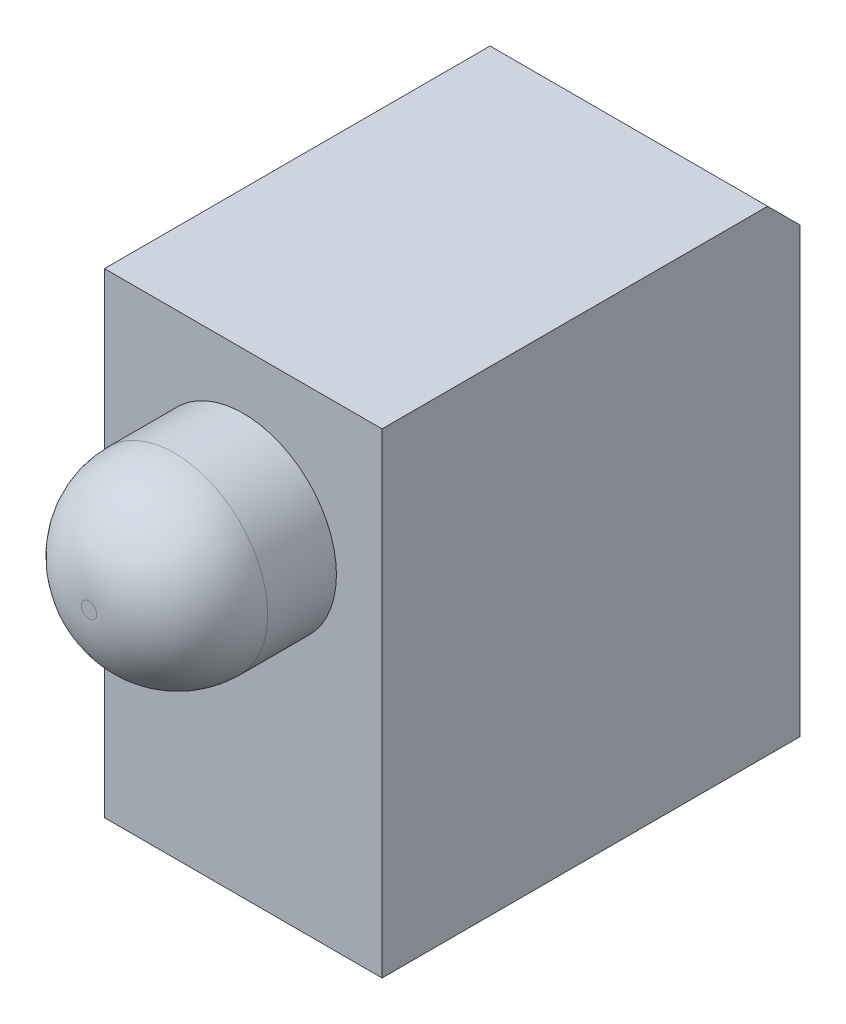
SolidWorks part; units mm, degrees
ref_plane "Front Plane" through (0, 0, 0) normal (0, 0, 1) x (1, 0, 0)
ref_plane "Top Plane" through (0, 0, 0) normal (0, 1, 0) x (1, 0, 0)
ref_plane "Right Plane" through (0, 0, 0) normal (1, 0, 0) x (0, 0, -1)
sketch "Sketch1" plane through (0, 0, 0) normal (1, 0, 0) x (0, 0, -1)
  line L1 (-3.25, -3.7) -> (3.25, -3.7)
  line L2 (-3.25, -3.7) -> (-3.25, 3.7)
  line L3 (-3.25, 3.7) -> (3.25, 3.7)
  line L4 (3.25, -3.7) -> (3.25, 3.7)
  line L5 (-3.25, -3.7) -> (3.25, 3.7) construction
  line L6 (-3.25, 3.7) -> (3.25, -3.7) construction
  point P0 (0, 0)
  dimension "D1" = 7.4
  dimension "D2" = 6.5
extrude "Boss-Extrude1" add sketch "Sketch1" along normal blind 2.16 and the other way blind 2.16
sketch "Sketch2" plane through (0, 0, 3.25) normal (0, 0, 1) x (1, 0, 0)
  line L0 (-2.16, -3.7) -> (2.16, -3.7) construction
  circle A0 centre (0, 1.38) radius 1.45
  dimension "D1" = 2.9
  dimension "D2" = 5.08
extrude "Boss-Extrude2" add sketch "Sketch2" along normal blind 2.4
fillet "Fillet1" radius 1.33 1 edges at (1.45, 1.38, 5.65)
chamfer "Chamfer1" distance 0.5 angle 45 1 edges at (0, 3.7, -3.25)
equation "\"D1@Boss-Extrude1\"=4.32/2"
equation "\"D2@Boss-Extrude1\"=4.32/2"
